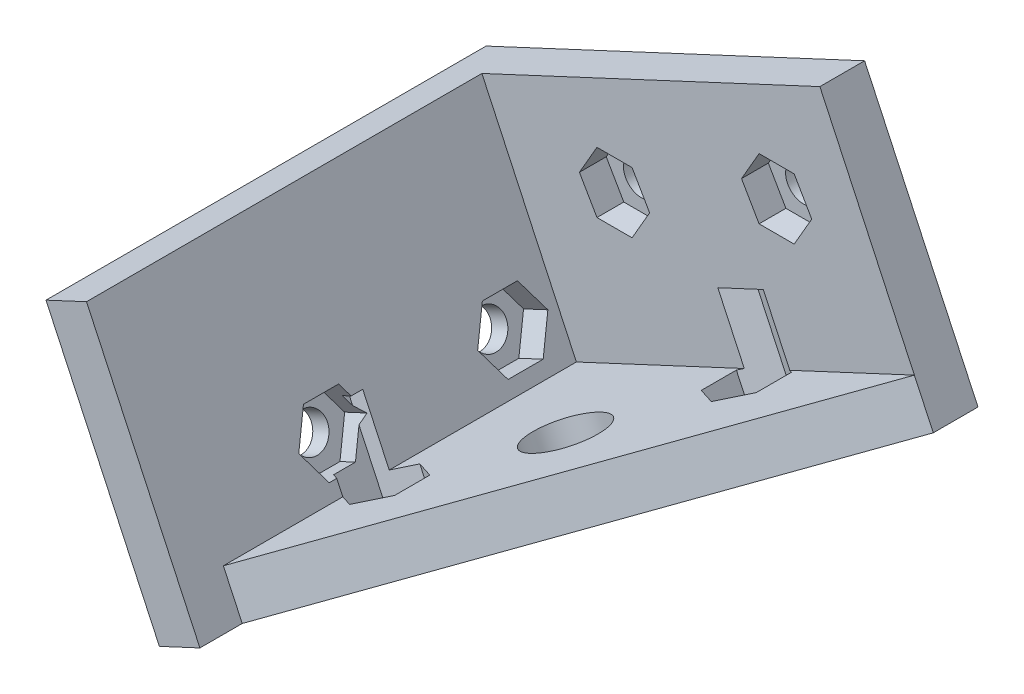
SolidWorks part; units mm, degrees
material "ABS"
ref_plane "Front Plane" through (0, 0, 0) normal (0, 0, 1) x (1, 0, 0)
ref_plane "Top Plane" through (0, 0, 0) normal (0, 1, 0) x (1, 0, 0)
ref_plane "Right Plane" through (0, 0, 0) normal (1, 0, 0) x (0, 0, -1)
sketch "Sketch1" plane through (0, 0, 0) normal (0, 0, 1) x (1, 0, 0)
  line L0 (-27.1677, -320.4736) -> (-39.8463, -293.2844)
  line L1 (-90.5605, -184.5274) -> (-56.751, -257.0321) construction
  line L2 (-39.8463, -293.2844) -> (2.4783, -273.5481)
  line L3 (2.4783, -273.5481) -> (15.1568, -300.7373)
  line L4 (332.3646, -152.8209) -> (-30.1585, -321.8683) construction
  line L5 (15.1568, -300.7373) -> (-27.1677, -320.4736)
  line L7 (-6.2846, -286.8374) -> (-4.3216, -290.2374)
  line L8 (-4.3216, -290.2374) -> (-0.3956, -290.2374)
  line L9 (-0.3956, -290.2374) -> (1.5674, -286.8374)
  line L10 (1.5674, -286.8374) -> (-0.3956, -283.4374)
  line L11 (-0.3956, -283.4374) -> (-4.3216, -283.4374)
  line L12 (-4.3216, -283.4374) -> (-6.2846, -286.8374)
  line L13 (-24.4107, -295.2897) -> (-22.4477, -298.6897)
  line L14 (-22.4477, -298.6897) -> (-18.5218, -298.6897)
  line L15 (-18.5218, -298.6897) -> (-16.5588, -295.2897)
  line L16 (-16.5588, -295.2897) -> (-18.5218, -291.8897)
  line L17 (-18.5218, -291.8897) -> (-22.4477, -291.8897)
  line L18 (-22.4477, -291.8897) -> (-24.4107, -295.2897)
  circle A0 centre (-2.3586, -286.8374) radius 2 construction
  circle A1 centre (-2.3586, -286.8374) radius 2
  circle A2 centre (-20.4847, -295.2897) radius 2
  circle A3 centre (-20.4847, -295.2897) radius 2 construction
  circle A4 centre (-2.3586, -286.8374) radius 3.4 construction
  circle A5 centre (-20.4847, -295.2897) radius 3.4 construction
  dimension "D1" = 10
  dimension "D2" = 10
  dimension "D3" = 6.8
  dimension "D4" = 6.8
extrude "Boss-Extrude1" add sketch "Sketch1" along normal blind 2 contours L5 L3 L2 L0 L18 L17 L16 L15 L14 L13 L12 L11 L10 L9 L8 L7 | L11 L12 L7 L8 L9 L10 A1 | L17 L18 L13 L14 L15 L16 A2 region at (-12.4007, -297.3715, 0) region at (-5.2131, -285.1893, 0) region at (-23.3393, -293.6417, 0)
extrude "Boss-Extrude2" add sketch "Sketch1<3>" along normal blind 3 from surface contours L5 L3 L2 L0 L18 L17 L16 L15 L14 L13 L12 L11 L10 L9 L8 L7 region at (-12.4007, -297.3715, 0) starting at face at (-12.3447, -297.0109, 2)
sketch "Sketch1<3>" plane through (0, 0, 0) normal (0, 0, 1) x (1, 0, 0) same geometry as "Sketch1"
sketch "Sketch3" plane through (117.8962, -252.8292, 0) normal (-0.4226, 0.9063, 0) x (0.9063, 0.4226, 0)
  line L0 (-113.3603, 0) -> (-113.3603, -5)
  line L1 (-113.3603, -5) -> (-160.0603, -49.2058)
  line L2 (-160.0603, 0) -> (-160.0603, -393.4) construction
  line L3 (-160.0603, -49.2058) -> (-160.0603, -5)
  line L5 (-149.3537, -26.5568) -> (-152.7537, -24.5938)
  line L6 (-152.7537, -24.5938) -> (-156.1537, -26.5568)
  line L7 (-156.1537, -26.5568) -> (-156.1537, -30.4828)
  line L8 (-156.1537, -30.4828) -> (-152.7537, -32.4458)
  line L9 (-152.7537, -32.4458) -> (-149.3537, -30.4828)
  line L10 (-149.3537, -30.4828) -> (-149.3537, -26.5568)
  line L11 (-131.5405, -3.3806) -> (-134.9405, -5.3436)
  line L12 (-134.9405, -5.3436) -> (-134.9405, -9.2696)
  line L13 (-134.9405, -9.2696) -> (-131.5405, -11.2326)
  line L14 (-131.5405, -11.2326) -> (-128.1405, -9.2696)
  line L15 (-128.1405, -9.2696) -> (-128.1405, -5.3436)
  line L16 (-128.1405, -5.3436) -> (-131.5405, -3.3806)
  line L17 (-113.3603, 0) -> (-160.0603, 0)
  line L18 (-160.0603, 0) -> (-160.0603, -5)
  circle A0 centre (-152.7537, -28.5198) radius 2 construction
  circle A1 centre (-131.5405, -7.3066) radius 2
  circle A2 centre (-152.7537, -28.5198) radius 2
  circle A3 centre (-152.7537, -28.5198) radius 3.4 construction
  circle A4 centre (-131.5405, -7.3066) radius 3.4 construction
  dimension "D1" = 10
  dimension "D2" = 4
  dimension "D3" = 4
  dimension "D4" = 6.8
  dimension "D5" = 6.8
extrude "Boss-Extrude3" add sketch "Sketch3" along normal blind 2 contours L17 L18 L3 L1 L0 L10 L9 L8 L7 L6 L5 L16 L15 L14 L13 L12 L11 | L15 L16 L11 L12 L13 L14 | L9 L10 L5 L6 L7 L8 region at (-11.8139, -313.314, 16.464) region at (-17.5584, -315.9927, 28.5198) region at (0.1737, -307.7241, 4.4521)
extrude "Boss-Extrude4" add sketch "Sketch3<4>" along normal blind 3 from surface contours L17 L18 L3 L1 L0 L10 L9 L8 L7 L6 L5 L16 L15 L14 L13 L12 L11 region at (-11.8139, -313.314, 16.464) starting at face at (-13.9048, -312.0822, 19.7353)
sketch "Sketch3<4>" plane through (117.8962, -252.8292, 0) normal (-0.4226, 0.9063, 0) x (0.9063, 0.4226, 0) same geometry as "Sketch3"
sketch "Sketch4" plane through (-145.0639, -67.6444, 0) normal (0.9063, 0.4226, 0) x (0, 0, -1)
  line L0 (-49.2058, -278.9662) -> (-49.2058, -248.9662)
  line L1 (-49.2058, -248.9662) -> (-5, -248.9662)
  line L2 (-5, -248.9662) -> (-5, -278.9662)
  line L3 (-5, -278.9662) -> (-49.2058, -278.9662)
  line L4 (-5, -248.9662) -> (0, -248.9662) construction
  line L6 (-33.926, -268.9662) -> (-31.963, -272.3662)
  line L7 (-31.963, -272.3662) -> (-28.037, -272.3662)
  line L8 (-28.037, -272.3662) -> (-26.074, -268.9662)
  line L9 (-26.074, -268.9662) -> (-28.037, -265.5662)
  line L10 (-28.037, -265.5662) -> (-31.963, -265.5662)
  line L11 (-31.963, -265.5662) -> (-33.926, -268.9662)
  line L12 (-13.926, -268.9662) -> (-11.963, -272.3662)
  line L13 (-11.963, -272.3662) -> (-8.037, -272.3662)
  line L14 (-8.037, -272.3662) -> (-6.074, -268.9662)
  line L15 (-6.074, -268.9662) -> (-8.037, -265.5662)
  line L16 (-8.037, -265.5662) -> (-11.963, -265.5662)
  line L17 (-11.963, -265.5662) -> (-13.926, -268.9662)
  circle A0 centre (-10, -268.9662) radius 2
  circle A1 centre (-30, -268.9662) radius 2
  circle A2 centre (-30, -268.9662) radius 3.4 construction
  circle A3 centre (-10, -268.9662) radius 3.4 construction
  point P14 (-27.0555, -267.2662)
  circle M11 centre (-30, -268.9662) radius 2
  circle M12 centre (-10, -268.9662) radius 2
  line M18 (-393.4, -278.9662) -> (0, -278.9662)
  dimension "D3" = 4
  dimension "D4" = 4
  dimension "D1" = 6.8
  dimension "D2" = 6.8
extrude "Boss-Extrude5" add sketch "Sketch4" along normal blind 2 contours L2 L1 L0 L17 L16 L15 L14 L13 L12 L11 L10 L9 L8 L7 L6 M18 | L10 L11 L6 L7 L8 L9 M11 | L16 L17 L12 L13 L14 L15 M12 region at (-33.6428, -306.5877, 27.5594) region at (-32.0904, -309.9169, 32.8545) region at (-32.0904, -309.9169, 12.8545)
extrude "Boss-Extrude6" add sketch "Sketch4<4>" along normal blind 3 from surface contours L2 L1 L0 L17 L16 L15 L14 L13 L12 L11 L10 L9 L8 L7 L6 M18 region at (-33.6428, -306.5877, 27.5594) starting at face at (-30.2857, -309.0548, 33.8395)
sketch "Sketch4<4>" plane through (-145.0639, -67.6444, 0) normal (0.9063, 0.4226, 0) x (0, 0, -1) same geometry as "Sketch4"
extrude "Cut-Extrude1" cut sketch "Sketch3<5>" along normal blind 10 from surface contours L15 L16 L11 L12 L13 L14 | L9 L10 L5 L6 L7 L8 region at (-17.5584, -315.9927, 28.5198) region at (0.1737, -307.7241, 4.4521) starting at face at (-3.9779, -307.4532, 7.3066)
sketch "Sketch3<5>" plane through (117.8962, -252.8292, 0) normal (-0.4226, 0.9063, 0) x (0.9063, 0.4226, 0) same geometry as "Sketch3"
sketch "Sketch5" plane through (117.8962, -252.8292, 0) normal (0.4226, -0.9063, 0) x (0.9063, 0.4226, 0)
  line L0 (-131.5405, 7.3066) -> (-152.7537, 28.5198) construction
  circle A0 centre (-142.1471, 17.9132) radius 4
  dimension "D1" = 8
extrude "Cut-Extrude2" cut sketch "Sketch5" against normal blind 10
